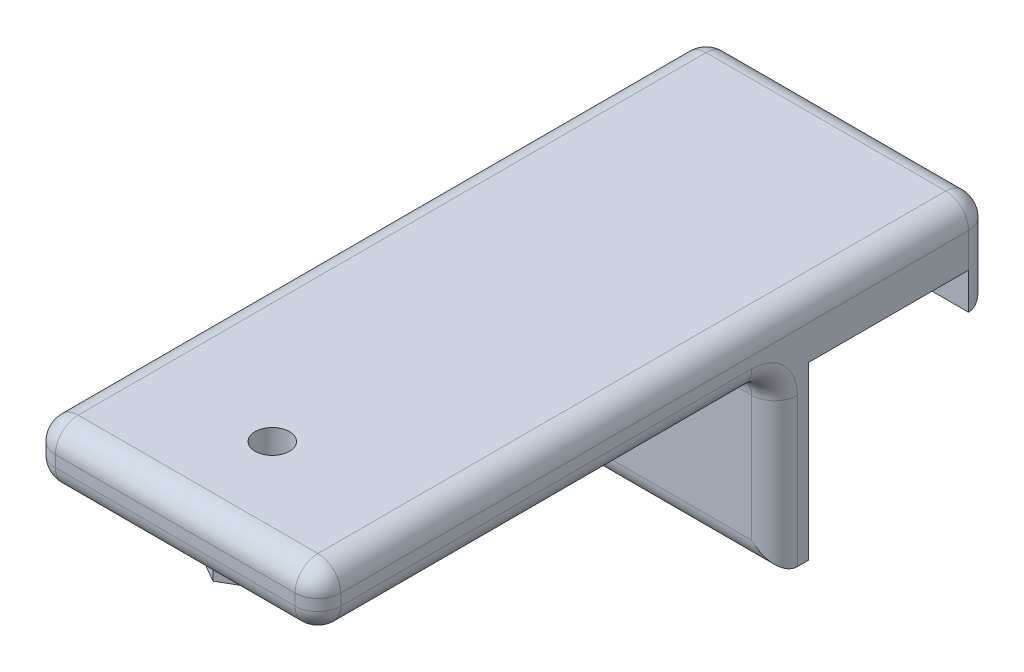
SolidWorks part; units mm, degrees
ref_plane "Front Plane" through (0, 0, 0) normal (0, 0, 1) x (1, 0, 0)
ref_plane "Top Plane" through (0, 0, 0) normal (0, 1, 0) x (1, 0, 0)
ref_plane "Right Plane" through (0, 0, 0) normal (1, 0, 0) x (0, 0, -1)
sketch "Sketch1" plane through (0, 0, 0) normal (0, 1, 0) x (1, 0, 0)
  line L1 (-12.5, -7) -> (12.5, -7)
  line L2 (-12.5, -7) -> (-12.5, 7)
  line L3 (-12.5, 7) -> (12.5, 7)
  line L4 (12.5, -7) -> (12.5, 7)
  line L5 (-12.5, -7) -> (12.5, 7) construction
  line L6 (-12.5, 7) -> (12.5, -7) construction
  point P0 (0, 0)
  dimension "D1" = 25
  dimension "D2" = 14
extrude "Boss-Extrude1" add sketch "Sketch1" along normal blind 5
sketch "Sketch2" plane through (0, 0, 7) normal (0, 0, 1) x (1, 0, 0)
  line L1 (-12.5, 0) -> (12.5, 0)
  line L2 (-12.5, 0) -> (-12.5, -15)
  line L3 (-12.5, -15) -> (12.5, -15)
  line L4 (-12.5, 0) -> (12.5, 0)
  line L5 (12.5, 0) -> (12.5, 5)
  line L6 (12.5, 5) -> (-12.5, 5)
  line L7 (-12.5, 5) -> (-12.5, 0)
  line L8 (-12.5, 0) -> (12.5, 0)
  line L9 (12.5, 0) -> (12.5, 5)
  line L10 (12.5, 5) -> (-12.5, 5)
  line L11 (-12.5, 5) -> (-12.5, 0)
  line L12 (12.5, 0) -> (12.5, -15)
  line M6 (-12.5, 0) -> (12.5, 0)
  line M7 (12.5, 0) -> (12.5, 5)
  line M8 (12.5, 5) -> (-12.5, 5)
  line M9 (-12.5, 5) -> (-12.5, 0)
  dimension "D2" = 15
  dimension "D1" = 0
extrude "Boss-Extrude2" add sketch "Sketch2" along normal blind 3 contours M9 M6 M7 M8 | L12 L2 L3 M6 region at (0, 2.5, 7) region at (0, -7.5, 7)
hole_wizard "M6 Clearance Hole1" positions "Sketch3" profile "Sketch4" hole size "M6" standard "ANSI Metric" end condition through all
sketch "Sketch3" plane through (0, 0, 10) normal (0, 0, 1) x (1, 0, 0)
  line L0 (-12.5, 0) -> (12.5, 0) construction
  line L1 (12.5, 5) -> (-12.5, 5) construction
  point P0 (0, -6.5)
  point P7 (0, 5)
  dimension "D1" = 6.5
sketch "Sketch4" plane through (0, -6.5, 10) normal (1, 0, 0) x (0, -1, 0)
  line L0 (0, 0) -> (0, 17)
  line L1 (0, 17) -> (3.3, 17)
  line L2 (3.3, 17) -> (3.3, 0)
  line L5 (3.3, 0) -> (0, 0)
  line L11 (0, -6.35) -> (0, 107.95) construction
  dimension "Thru Hole Dia." = 6.6
  dimension "Thru Hole Depth" = 17
sketch "Sketch10" plane through (0, 0, -7) normal (0, 0, -1) x (-1, 0, 0)
  line L0 (-12.5, -3.2) -> (12.5, -3.2)
  line L4 (12.5, -15) -> (12.5, 0)
  line L5 (12.5, 0) -> (-12.5, 0)
  line L6 (-12.5, 0) -> (-12.5, -15)
  line L7 (-12.5, -15) -> (12.5, -15)
  line L8 (12.5, -15) -> (12.5, 0)
  line L9 (12.5, 0) -> (-12.5, 0)
  line L10 (-12.5, 0) -> (-12.5, -15)
  line L11 (-12.5, -15) -> (12.5, -15)
  circle A0 centre (0, -6.5) radius 3.3 construction
  circle A1 centre (0, -6.5) radius 3.3
  line M6 (-12.5, 0) -> (12.5, 0)
  line M7 (12.5, 0) -> (12.5, 5)
  line M8 (12.5, 5) -> (-12.5, 5)
  line M9 (-12.5, 5) -> (-12.5, 0)
  dimension "D1" = 0
extrude "Boss-Extrude5" add sketch "Sketch10" along normal blind 2 contours L10 L0 L8 M6 | M9 M6 M7 M8 region at (0, -1.6, -7) region at (0, 2.5, -7)
sketch "Sketch5" plane through (0, 0, 10) normal (0, 0, 1) x (1, 0, 0)
  line L1 (-12.5, 0) -> (12.5, 0) construction
  line L2 (-12.5, 0) -> (12.5, 0)
  line L4 (-12.5, 5) -> (-12.5, -15)
  line L5 (-12.5, -15) -> (12.5, -15)
  line L6 (12.5, -15) -> (12.5, 5)
  line L7 (12.5, 5) -> (-12.5, 5)
  line L8 (-12.5, 5) -> (-12.5, -15)
  line L9 (-12.5, -15) -> (12.5, -15)
  line L10 (12.5, -15) -> (12.5, 5)
  line L11 (12.5, 5) -> (-12.5, 5)
  line M6 (-12.5, 5) -> (-12.5, -15)
  line M8 (12.5, -15) -> (12.5, 5)
  line M9 (12.5, 5) -> (-12.5, 5)
  dimension "D1" = 0
extrude "Boss-Extrude4" add sketch "Sketch5" along normal blind 40 contours M8 M9 M6 region at (0, 2.5, 10)
sketch "Sketch9" plane through (0, 5, 0) normal (0, 1, 0) x (1, 0, 0)
  line L4 (12.5, -50) -> (12.5, 9)
  line L5 (12.5, 9) -> (-12.5, 9)
  line L6 (-12.5, 9) -> (-12.5, -50)
  line L7 (12.5, 9) -> (-12.5, 9)
  line L8 (12.5, -50) -> (12.5, 9)
  line L10 (-12.5, 9) -> (-12.5, -50)
  line L12 (-12.5, -50) -> (12.5, -50)
  line L14 (-12.5, -50) -> (12.5, -50)
  circle A0 centre (0, -41.5) radius 1.5
  dimension "D2" = 3
  dimension "D1" = 0
extrude "Cut-Extrude1" cut sketch "Sketch9" against normal up to next contours A0 region at (0, 5, 41.5)
fillet "Fillet1" radius 2 16 edges at (-12.5, 0, 30) (12.5, 0, 30) (0, -15, 10) (0, -3.2, -9) (0, 5, -9) (12.5, 5, 20.5) (0, 5, 50) (-12.5, 5, 20.5) (0, 0, 50) (0, 0, 10) (12.5, -7.5, 10) (-12.5, -7.5, 10) (12.5, 0.9, -9) (-12.5, 0.9, -9) (12.5, 2.5, 50) (-12.5, 2.5, 50)
sketch "Sketch11" plane through (0, 0, 0) normal (0, -1, 0) x (1, 0, 0)
  line L0 (-10.5, 48) -> (-10.5, 12) construction
  line L1 (-3, 43.2321) -> (-3, 39.7679)
  line L2 (-3, 39.7679) -> (0, 38.0359)
  line L3 (0, 38.0359) -> (3, 39.7679)
  line L4 (3, 39.7679) -> (3, 43.2321)
  line L5 (3, 43.2321) -> (0, 44.9641)
  line L6 (0, 44.9641) -> (-3, 43.2321)
  line L7 (0, 46.6962) -> (-4.5, 44.0981)
  line L8 (-4.5, 44.0981) -> (-4.5, 38.9019)
  line L9 (-4.5, 38.9019) -> (0, 36.3038)
  line L10 (0, 36.3038) -> (4.5, 38.9019)
  line L11 (4.5, 38.9019) -> (4.5, 44.0981)
  line L12 (4.5, 44.0981) -> (0, 46.6962)
  circle A0 centre (0, 41.5) radius 1.5 construction
  circle A1 centre (0, 41.5) radius 1.5
  circle A2 centre (0, 41.5) radius 3 construction
  dimension "D1" = 6
  dimension "D2" = 1.5
extrude "Boss-Extrude6" add sketch "Sketch11" along normal blind 3 contours L11 L12 L7 L8 L9 L10 L6 L5 L4 L3 L2 L1 region at (2.1813, 0, 45.2781)
